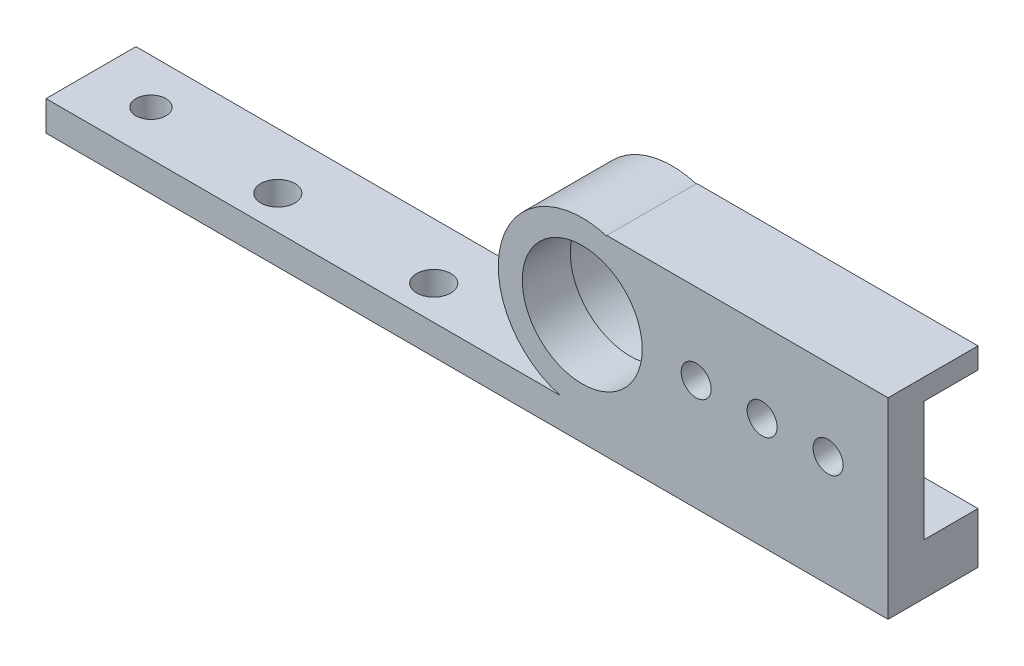
SolidWorks part; units mm, degrees
ref_plane "前视基准面" through (0, 0, 0) normal (0, 0, 1) x (1, 0, 0)
ref_plane "上视基准面" through (0, 0, 0) normal (0, 1, 0) x (1, 0, 0)
ref_plane "右视基准面" through (0, 0, 0) normal (1, 0, 0) x (0, 0, -1)
sketch "草图1" plane through (0, 0, 0) normal (0, 0, 1) x (1, 0, 0)
  line L1 (20, -10) -> (-20, -10)
  line L2 (20, -10) -> (20, 10)
  line L3 (20, 10) -> (-20, 10)
  line L4 (-20, -10) -> (-20, 10)
  line L5 (20, -10) -> (-20, 10) construction
  line L6 (20, 10) -> (-20, -10) construction
  point P0 (0, 0)
  dimension "D1" = 40
  dimension "D2" = 20
extrude "凸台-拉伸1" add sketch "草图1" along normal blind 6
sketch "草图2" plane through (0, 0, 6) normal (0, 0, 1) x (1, 0, 0)
  line L0 (20, -10) -> (20, 10) construction
  circle A0 centre (10, 0) radius 2.5
  circle A1 centre (-1, 0) radius 2.5
  circle A2 centre (-12, 0) radius 2.5
  dimension "D1" = 10
  dimension "D2" = 5
  dimension "D3" = 3
extrude "切除-拉伸1" cut sketch "草图2" against normal through all
sketch "草图3" plane through (0, 0, 6) normal (0, 0, 1) x (1, 0, 0)
  line L0 (20, 13.5) -> (20, 10)
  line L1 (20, -13.5) -> (-26.894, -13.5)
  line L3 (20, 13.5) -> (-26.894, 13.5)
  line L4 (-20, 10) -> (-20, -10)
  line L5 (-20, -10) -> (20, -10)
  line L6 (20, -10) -> (20, 10)
  line L7 (20, 10) -> (-20, 10)
  line L8 (-20, 10) -> (-20, -10)
  line L9 (-20, -10) -> (20, -10)
  line L10 (20, -10) -> (20, 10)
  line L11 (20, 10) -> (-20, 10)
  line L12 (-26.894, -13.5) -> (-26.894, 13.5)
  line L13 (20, -10.0394) -> (-26.894, 13.5) construction
  line L14 (20, 10.0394) -> (-26.894, -13.5) construction
  line L15 (20, -10) -> (20, -13.5)
  circle A0 centre (-31, 0) radius 11
  circle A1 centre (-31, 0) radius 14
  point P2 (0, 0)
  line M10 (-20, 10) -> (-20, -10)
  line M11 (-20, -10) -> (20, -10)
  line M13 (20, 10) -> (-20, 10)
  dimension "D3" = 22
  dimension "D4" = 28
  dimension "D2" = 3.5
  dimension "D1" = 0
extrude "凸台-拉伸2" add sketch "草图3" against normal blind 15 contours L3 A1 L1 L12 A0 | A1 L1 L15 M11 M10 | L1 A1 L8 A0 L12 | L8 A1 L3 L12 A0 | L8 A1 | A1 L0 L3 M10 M13 region at (-1.9449, 11.7771, 6) region at (-1.9449, -11.7771, 6) region at (-23.0173, 9.0328, 6) region at (-27.2274, 11.7946, 6) region at (-18.7882, 0, 6) region at (-23.0173, -9.0328, 6)
sketch "草图5" plane through (0, 0, 6) normal (0, 0, 1) x (1, 0, 0)
  circle A0 centre (-31, 0) radius 10
  circle A1 centre (-31, 0) radius 11 construction
  circle A2 centre (-31, 0) radius 11
  dimension "D1" = 20
extrude "凸台-拉伸3" add sketch "草图5" against normal blind 8
sketch "草图6" plane through (0, 0, 6) normal (0, 0, 1) x (1, 0, 0)
  circle A0 centre (-31, 0) radius 8.5
  circle A1 centre (-31, 0) radius 10 construction
  circle A2 centre (-31, 0) radius 10
  dimension "D1" = 17
sketch "草图9" plane through (0, -13.5, 0) normal (0, -1, 0) x (1, 0, 0)
  circle A0 centre (-18.2368, -1.344) radius 5.5352
sketch "草图10" plane through (20, 0, 0) normal (1, 0, 0) x (0, 0, -1)
  line L1 (9, -13.5) -> (-6, -13.5)
  line L2 (9, -13.5) -> (9, -18.5)
  line L3 (9, -18.5) -> (-6, -18.5)
  line L4 (-6, -13.5) -> (-6, -18.5)
  dimension "D1" = 5
extrude "凸台-拉伸4" add sketch "草图10" against normal blind 200
sketch "草图11" plane through (0, 0, 6) normal (0, 0, 1) x (1, 0, 0)
  line L1 (-28.6193, -11.8661) -> (-25.5243, -11.8661)
  line L2 (-28.6193, -11.8661) -> (-28.6193, -14.961)
  line L3 (-28.6193, -14.961) -> (-25.5243, -14.961)
  line L4 (-25.5243, -11.8661) -> (-25.5243, -14.961)
extrude "凸台-拉伸5" add sketch "草图11" against normal through all
sketch "草图13" plane through (0, -18.5, 0) normal (0, -1, 0) x (1, 0, 0)
  line L0 (-154.7729, 6) -> (-154.7729, -9)
  line L1 (-180, 6) -> (20, 6) construction
  line L2 (-154.7729, 124.91) -> (-154.7729, -245.09) construction
  line L3 (-180, -9) -> (20, -9) construction
sketch "草图14" plane through (0, -18.5, 0) normal (0, -1, 0) x (1, 0, 0)
  line L0 (-120.4266, -15.7251) -> (-120.4266, 9.3691)
  line L1 (-120.4266, 125.09) -> (-120.4266, -244.91) construction
sketch "草图15" plane through (0, -18.5, 0) normal (0, -1, 0) x (1, 0, 0)
  line L1 (-120.4266, -15.7251) -> (-184.1416, -15.7251)
  line L2 (-120.4266, -15.7251) -> (-120.4266, 11.9644)
  line L3 (-120.4266, 11.9644) -> (-184.1416, 11.9644)
  line L4 (-184.1416, -15.7251) -> (-184.1416, 11.9644)
sketch "草图16" plane through (0, -18.5, 0) normal (0, -1, 0) x (1, 0, 0)
  line L0 (-120.4266, -17.1171) -> (-120.4266, 37.1771)
  line L1 (-120.4266, 125.09) -> (-120.4266, -244.91) construction
sketch "草图17" plane through (0, -18.5, 0) normal (0, -1, 0) x (1, 0, 0)
  line L1 (-120.4266, -17.1171) -> (-191.9094, -17.1171)
  line L2 (-120.4266, -17.1171) -> (-120.4266, 25.2398)
  line L3 (-120.4266, 25.2398) -> (-191.9094, 25.2398)
  line L4 (-191.9094, -17.1171) -> (-191.9094, 25.2398)
extrude "切除-拉伸2" cut sketch "草图17" against normal through all
sketch "草图20" plane through (0, -18.5, 0) normal (0, -1, 0) x (1, 0, 0)
  line L0 (-120.4266, 6) -> (-120.4266, -9) construction
  line L1 (-120.4266, -1.5) -> (-110.4266, -1.5) construction
  circle A0 centre (-110.4266, -1.5) radius 2.5
  dimension "D1" = 5
  dimension "D2" = 10
extrude "切除-拉伸3" cut sketch "草图20" against normal through all
sketch "草图21" plane through (0, -18.5, 0) normal (0, -1, 0) x (1, 0, 0)
  circle A0 centre (-87.421, 0.3438) radius 2.8371
  circle A1 centre (-61.421, 0.3438) radius 2.8371
extrude "切除-拉伸4" cut sketch "草图21" against normal through all
